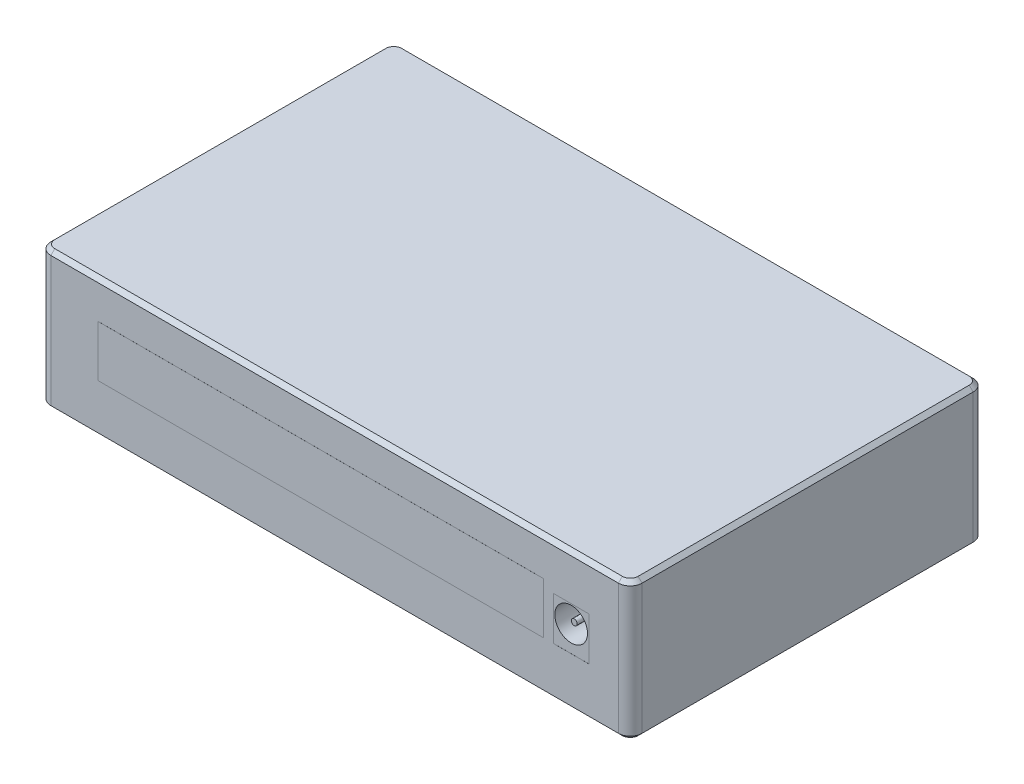
SolidWorks part; units mm, degrees
ref_plane "前视基准面" through (0, 0, 0) normal (0, 0, 1) x (1, 0, 0)
ref_plane "上视基准面" through (0, 0, 0) normal (0, 1, 0) x (1, 0, 0)
ref_plane "右视基准面" through (0, 0, 0) normal (1, 0, 0) x (0, 0, -1)
other "Configuration Table"
sketch "草图1" plane through (0, 0, 0) normal (0, 1, 0) x (1, 0, 0)
  line L0 (41.7512, 0) -> (191.7512, 0)
  line L1 (191.7512, 0) -> (191.7512, 90)
  line L2 (191.7512, 90) -> (41.7512, 90)
  line L3 (41.7512, 90) -> (41.7512, 0)
extrude "凸台-拉伸1" add sketch "草图1" along normal blind 35
sketch "草图2" plane through (0, 0, 0) normal (0, -1, 0) x (1, 0, 0)
  circle A0 centre (173.7512, -18) radius 5
  circle A1 centre (59.7512, -18) radius 5
  circle A2 centre (59.7512, -72) radius 5
  circle A3 centre (173.7512, -72) radius 5
extrude "凸台-拉伸2" add sketch "草图2" along normal blind 1.8
fillet "圆角1" radius 3 4 edges at (191.7512, 17.5, 0) (191.7512, 17.5, -90) (41.7512, 17.5, 0) (41.7512, 17.5, -90)
chamfer "倒角1" distance 1 angle 45 16 edges at (116.7512, 35, 0) (190.8726, 35, -0.8787) (42.6299, 35, -0.8787) (191.7512, 35, -45) (41.7512, 35, -45) (190.8726, 35, -89.1213) (42.6299, 35, -89.1213) (116.7512, 35, -90) (116.7512, 0, 0) (190.8726, 0, -0.8787) (42.6299, 0, -0.8787) (191.7512, 0, -45) (41.7512, 0, -45) (190.8726, 0, -89.1213) (42.6299, 0, -89.1213) (116.7512, 0, -90)
chamfer "倒角2" distance 1.8 angle 45 4 edges at (59.7512, -1.8, -77) (59.7512, -1.8, -23) (173.7512, -1.8, -77) (173.7512, -1.8, -23)
sketch "草图3" plane through (0, 0, 0) normal (0, 0, 1) x (1, 0, 0)
  circle A0 centre (176.7512, 19) radius 4.15
extrude "切除-拉伸1" cut sketch "草图3" against normal blind 5.8
sketch "草图4" plane through (0, 0, -5.8) normal (0, 0, 1) x (1, 0, 0)
  circle A0 centre (176.7512, 19) radius 0.75
extrude "凸台-拉伸3" add sketch "草图4" along normal blind 5
sketch "草图5" plane through (0, 0, 0) normal (0, 0, 1) x (1, 0, 0)
  line L1 (176.7512, 23.5) -> (172.2512, 23.5)
  line L2 (172.2512, 23.5) -> (172.2512, 12.5)
  line L3 (172.2512, 12.5) -> (181.2512, 12.5)
  line L4 (181.2512, 12.5) -> (181.2512, 23.5)
  line L5 (181.2512, 23.5) -> (176.7512, 23.5)
extrude "切除-拉伸2" cut sketch "草图5" against normal blind 0.01
sketch "草图6" plane through (0, 0, 0) normal (0, 0, 1) x (1, 0, 0)
  line L3 (169.7512, 12.5) -> (56.7512, 12.5)
  line L4 (56.7512, 12.5) -> (56.7512, 25.5)
  line L5 (56.7512, 25.5) -> (169.7512, 25.5)
  line L6 (169.7512, 25.5) -> (169.7512, 12.5)
extrude "凸台-拉伸4" add sketch "草图6" along normal blind 0.01
